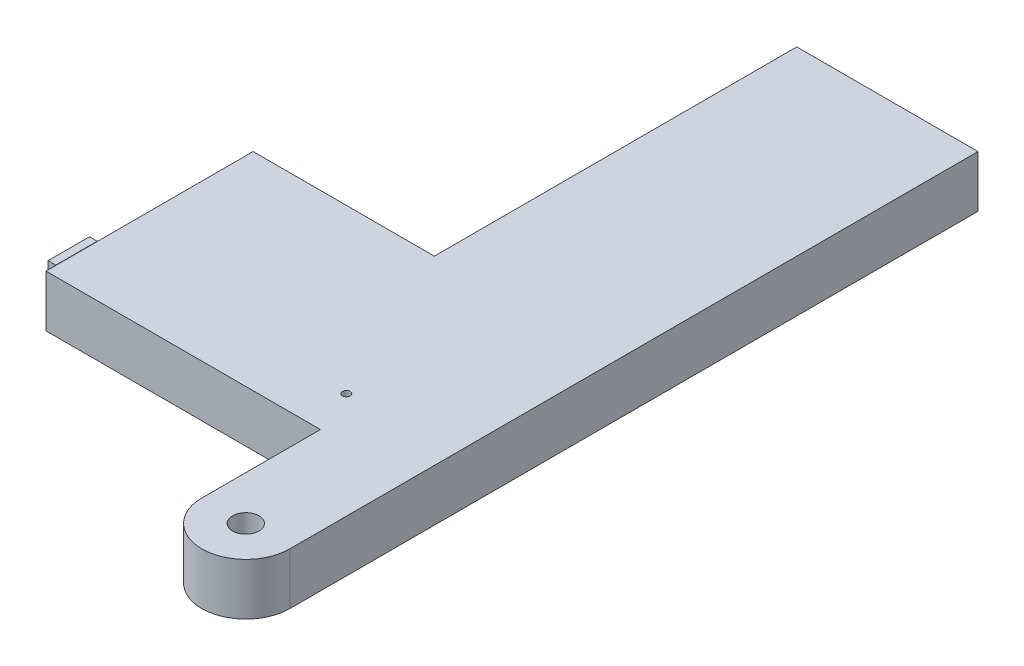
SolidWorks part; units mm, degrees
ref_plane "Front Plane" through (0, 0, 0) normal (0, 0, 1) x (1, 0, 0)
ref_plane "Top Plane" through (0, 0, 0) normal (0, 1, 0) x (1, 0, 0)
ref_plane "Right Plane" through (0, 0, 0) normal (1, 0, 0) x (0, 0, -1)
sketch "CornerrSketch1" plane through (0, 0, 0) normal (0, 1, 0) x (1, 0, 0)
  line L0 (0, 0) -> (0, 80)
  line L5 (0, 80) -> (70, 80)
  line L6 (70, 80) -> (70, 220)
  line L7 (140, 220) -> (70, 220)
  line L8 (106, -45.825) -> (106, 0)
  line L9 (0, 0) -> (106, 0)
  line L10 (140, 220) -> (140, -45.825)
  arc A0 (106, -45.825) -> (140, -45.825) centre (123, -45.825) ccw
  dimension "D5" = 34
  dimension "D4" = 80
  dimension "D3" = 70
  dimension "D1" = 220
  dimension "D2" = 45.825
  dimension "D6" = 140
extrude "CornerBoss-Extrude1" add sketch "CornerrSketch1" along normal blind 20
shell "Shell1" thickness 3 removed face at (79, 0, -61.4188)
sketch "PadSketch1" plane through (0, 17, 0) normal (0, -1, 0) x (1, 0, 0)
  line L1 (0, 0) -> (106, 0) construction
  line L2 (140, 45.825) -> (140, -220) construction
  circle A0 centre (99, -17) radius 5
  circle A1 centre (123, 45.825) radius 12
  dimension "D1" = 10
  dimension "D4" = 24
  dimension "D3" = 17
  dimension "D2" = 41
extrude "PadBoss-Extrude1" add sketch "PadSketch1" along normal blind 10
sketch "StepperShaftCut-Sketch3" plane through (0, 7, 0) normal (0, -1, 0) x (1, 0, 0)
  circle A0 centre (123, 45.825) radius 5.1
  circle A1 centre (99, -17) radius 1.5
  dimension "D2" = 3
  dimension "D1" = 10.2
extrude "StepperShaftCut-Extrude1" cut sketch "StepperShaftCut-Sketch3" against normal through all
sketch "ThreadedNutMountHolesSketch5" plane through (0, 7, 0) normal (0, -1, 0) x (1, 0, 0)
  circle A0 centre (123, 53.825) radius 1
  circle A1 centre (131, 45.825) radius 1
  circle A2 centre (115, 45.825) radius 1
  circle A3 centre (123, 37.825) radius 1
  dimension "D3" = 2
  dimension "D1" = 8
  dimension "D2" = 16
  dimension "D4" = 8
  dimension "D5" = 16
extrude "ThreadedNutMountHolesCut-Extrude2" cut sketch "ThreadedNutMountHolesSketch5" against normal blind 10
sketch "TopPegHoleSketch4" plane through (0, 0, -220) normal (0, 0, -1) x (-1, 0, 0)
  line L1 (-130, 14) -> (-120, 14)
  line L2 (-130, 14) -> (-130, 0)
  line L3 (-130, 0) -> (-120, 0)
  line L4 (-120, 14) -> (-120, 0)
  line L5 (-140, 0) -> (-70, 0) construction
  line L6 (-140, 20) -> (-140, 0) construction
  dimension "D2" = 10
  dimension "D3" = 14
  dimension "D1" = 10
extrude "TopPegHoleCut-Extrude2" cut sketch "TopPegHoleSketch4" against normal blind 3
sketch "BLPegSketch5" plane through (0, 0, 0) normal (-1, 0, 0) x (0, 0, 1)
  line L1 (-19.9, 13.9) -> (-10.1, 13.9)
  line L2 (-19.9, 13.9) -> (-19.9, 0)
  line L3 (-19.9, 0) -> (-10.1, 0)
  line L4 (-10.1, 13.9) -> (-10.1, 0)
  line L5 (-80, 0) -> (0, 0) construction
  line L6 (0, 20) -> (0, 0) construction
  dimension "D2" = 13.9
  dimension "D3" = 9.8
  dimension "D1" = 10.1
extrude "BLPegBoss-Extrude3" add sketch "BLPegSketch5" along normal blind 3.1
sketch "BLPegCapSketch6" plane through (-3.1, 0, 0) normal (-1, 0, 0) x (0, 0, 1)
  line L0 (-19.9, 13.9) -> (-19.9, 0) construction
  line L1 (-22.9, 17) -> (-6.9, 17)
  line L2 (-22.9, 17) -> (-22.9, 0)
  line L3 (-22.9, 0) -> (-6.9, 0)
  line L4 (-6.9, 17) -> (-6.9, 0)
  line L8 (-19.9, 0) -> (-10.1, 0) construction
  dimension "D1" = 16
  dimension "D3" = 17
  dimension "D2" = 3
extrude "BLPegCapBoss-Extrude4" add sketch "BLPegCapSketch6" along normal blind 3
sketch "BedCenterPegHoleCutSketch1" plane through (70, 0, 0) normal (-1, 0, 0) x (0, 0, 1)
  line L0 (-220, 0) -> (-80, 0) construction
  line L1 (-190, 14) -> (-180, 14)
  line L2 (-190, 14) -> (-190, 0)
  line L3 (-190, 0) -> (-180, 0)
  line L4 (-180, 14) -> (-180, 0)
  line L5 (-80, 20) -> (-80, 0) construction
  dimension "D2" = 10
  dimension "D1" = 14
  dimension "D3" = 100
extrude "BedCenterPegHoleCut-Extrude1" cut sketch "BedCenterPegHoleCutSketch1" against normal blind 3
equation "\"BedThickness\"= 20mm"
equation "\"BedToBuildPlateStandoffHolesDistanceFromLeftOrRight\"= \"BuildPlateStandoffHolesDistanceFromLeftOrRight\" + \"BedIncreasedByWidth\" / 2'Equals 17"
equation "\"BedToBuildPlateStandoffHoleSize\"= 3mm"
equation "\"BedLLongSide\"= \"BedThirdSize\" * 3'Equals 210"
equation "\"BedLShortSide\"= \"BedThirdSize\" * 2'Equals 140"
equation "\"BedLWidth\"= \"BedThirdSize\"'Equals 70"
equation "\"D4@CornerrSketch1\"=\"BedLWidth\" + \"BedIncreasedByWidth\"/2"
equation "\"BedIncreasedByWidth\"= 20mm"
equation "\"BedIncreasedByLength\"= 0mm"
equation "\"BedThirdSize\"= 70mm"
equation "\"StandardWallThickness\"= 3mm"
equation "\"D2@TopPegHoleSketch4\"=\"BedPegHoleWidth\""
equation "\"D3@TopPegHoleSketch4\"=\"BedPegHoleHeight\""
equation "\"D1@TopPegHoleCut-Extrude2\" = \"StandardWallThickness\""
equation "\"D3@BLPegSketch5\"=\"BedPegWidth\""
equation "\"D1@BLPegBoss-Extrude3\"=\"BedPegBoss\""
equation "\"D2@BLPegSketch5\"=\"BedPegHeight\""
equation "\"D2@BLPegCapSketch6\"=\"StandardWallThickness\""
equation "\"D3@BLPegCapSketch6\"=\"BedPegCapHeight\""
equation "\"D1@BLPegCapBoss-Extrude4\" = \"StandardWallThickness\""
equation "\"D3@CornerrSketch1\"=\"BedLWidth\" "
equation "\"D1@PadSketch1\" = \"BedToBuildPlateStandoffPadSize\""
equation "\"D1@PadBoss-Extrude1\"=\"LeadScrewNutPadDepth\""
equation "\"BedToBuildPlateStandoffPadSize\"= 10mm"
equation "\"BedToBuildPlateStandoffHolesDistanceFromBack\"= \"BuildPlateStandoffHolesDistanceFromBack\" + \"BedIncreasedByLength\" / 2'Equals 41"
equation "\"BuildPlateStandoffHolesDistanceFromLeftOrRight\"= 7mm"
equation "\"BuildPlateStandoffHolesDistanceFromBack\"= 41mm"
equation "\"DistanceFromBedSideToStepperHole\"= ( \"DistanceBetweenLeftToRightStepperHoles\" - \"BedWidth\" ) / 2'Equals 45.825"
equation "\"DistanceBetweenLeftToRightStepperHoles\"= \"FrontBackRailLength\" - \"StepperMountingHoleOffsetFromLeftOrRightSide\" * 2 - \"StepperMountingHoleDistance\"'Equals 461.65"
equation "\"FrontBackRailLength\"= 510mm"
equation "\"StepperMountingHoleOffsetFromLeftOrRightSide\"= \"StepperMountingHoleOffsetFromItsSide\" + \"RailThickness\""
equation "\"StepperMountingHoleDistance\"= 31mm'Spec"
equation "\"StepperMountingHoleOffsetFromItsSide\"= 5.5mm'Spec"
equation "\"RailThickness\"= .125in'Spec"
equation "\"BedWidth\"= \"BedInnerSquareWidth\" + \"BedLWidth\" * 2 + \"BedIncreasedByWidth\"'Equals 370"
equation "\"BedInnerSquareWidth\"= \"BedThirdSize\" * 3'Equals 210"
equation "\"D1@CornerrSketch1\"=\"BedLLongSide\"  + \"BedIncreasedByWidth\"/2"
equation "\"D2@CornerrSketch1\"=\"DistanceFromBedSideToStepperHole\""
equation "\"D3@PadSketch1\"=\"BedToBuildPlateStandoffHolesDistanceFromLeftOrRight\""
equation "\"D2@PadSketch1\"=\"BedToBuildPlateStandoffHolesDistanceFromBack\""
equation "\"D1@TopPegHoleSketch4\"=\"BedTopPegOffsetFromSide\""
equation "\"D1@BLPegSketch5\"=\"BedTopPegOffsetFromSide\" + .1mm"
equation "\"D6@CornerrSketch1\"=\"BedLShortSide\" + \"BedIncreasedByLength\"/2"
equation "\"LeadScrewNutPadSize\"= \"LeadScrewNutMountingHoleFlangeDiameter\" + 2mm'Equals 24"
equation "\"D4@PadSketch1\"=\"LeadScrewNutPadSize\""
equation "\"D1@StepperShaftCut-Sketch3\"=\"LeadScrewNutInnerShaftFlangeDiameter\""
equation "\"D2@StepperShaftCut-Sketch3\" = \"BedToBuildPlateStandoffHoleSize\""
equation "\"LeadScrewNutInnerShaftFlangeDiameter\"= 10.2mm'Spec"
equation "\"LeadScrewNutMountHoleDiameter\"= 2mm'Spec is 4.1 but smaller for tapping"
equation "\"LeadScrewNutMountingHoleFlangeDiameter\"= 22mm'Spec"
equation "\"LeadScrewNutMountingHoleDistance\"= 16mm'Spec"
equation "\"D1@ThreadedNutMountHolesSketch5\"=\"LeadScrewNutMountingHoleDistance\"/2"
equation "\"D2@ThreadedNutMountHolesSketch5\"=\"LeadScrewNutMountingHoleDistance\""
equation "\"D4@ThreadedNutMountHolesSketch5\"=\"LeadScrewNutMountingHoleDistance\"/2"
equation "\"D5@ThreadedNutMountHolesSketch5\"=\"LeadScrewNutMountingHoleDistance\""
equation "\"D3@ThreadedNutMountHolesSketch5\"=\"LeadScrewNutMountHoleDiameter\""
equation "\"LeadScrewNutPadDepth\"= \"BedThickness\" / 2'Equals 10"
equation "\"D1@ThreadedNutMountHolesCut-Extrude2\"= \"LeadScrewNutPadDepth\""
equation "\"BedPegHoleWidth\"= 10mm"
equation "\"BedPegHoleHeight\"= \"BedThickness\" - \"StandardWallThickness\" * 2'Equals 14"
equation "\"BedPegWidth\"= \"BedPegHoleWidth\" - .1mm * 2'For easier assembly"
equation "\"BedPegHeight\"= \"BedPegHoleHeight\" - .1mm'For easier assembly"
equation "\"BedTopPegOffsetFromSide\"= 10mm"
equation "\"BedPegBoss\"= \"StandardWallThickness\" + .1mm'For easier assembly"
equation "\"BedPegCapHeight\"= \"BedThickness\" - \"StandardWallThickness\"'Equals 17"
equation "\"BedPegCapWidth\"= \"BedThickness\" / 2 + \"StandardWallThickness\" * 2'Equals 16"
equation "\"D1@BLPegCapSketch6\"=\"BedPegCapWidth\""
equation "\"D1@BedCenterPegHoleCutSketch1\" = \"BedPegHoleHeight\""
equation "\"D3@BedCenterPegHoleCutSketch1\" = \"BedInnerSquareWidth\" / 2 - \"BedPegHoleWidth\" / 2"
equation "\"D2@BedCenterPegHoleCutSketch1\" = \"BedPegHoleWidth\""
equation "\"D1@BedCenterPegHoleCut-Extrude1\"=\"StandardWallThickness\""
